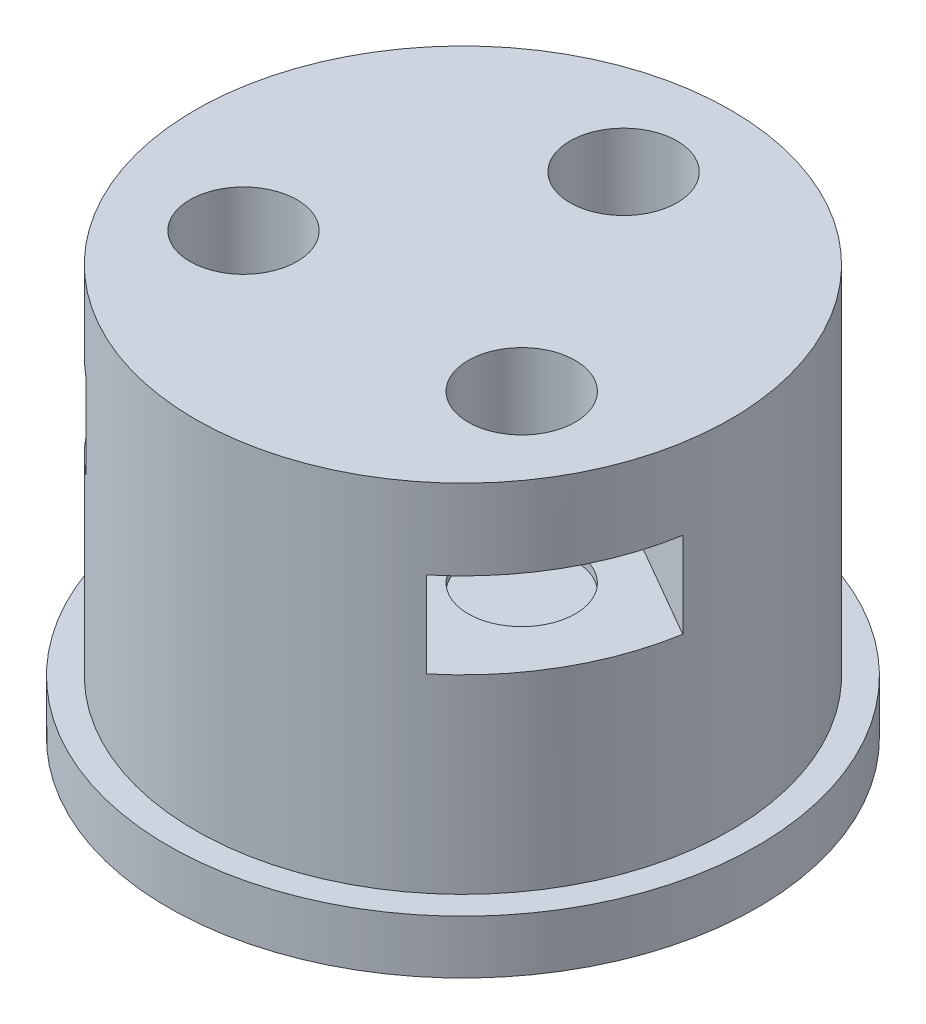
SolidWorks part; units mm, degrees
ref_plane "Front Plane" through (0, 0, 0) normal (0, 0, 1) x (1, 0, 0)
ref_plane "Top Plane" through (0, 0, 0) normal (0, 1, 0) x (1, 0, 0)
ref_plane "Right Plane" through (0, 0, 0) normal (1, 0, 0) x (0, 0, -1)
sketch "Sketch1" plane through (0, 0, 0) normal (0, 1, 0) x (1, 0, 0)
  circle A0 centre (0, 0) radius 10
  circle A1 centre (0, 0) radius 6 construction
  dimension "D1" = 20
  dimension "D2" = 12
extrude "Boss-Extrude1" add sketch "Sketch1" along normal blind 15.3
sketch "Sketch2" plane through (0, 0, 0) normal (0, -1, 0) x (1, 0, 0)
  circle A0 centre (0, 0) radius 10 construction
  circle A1 centre (0, 0) radius 10
  circle A2 centre (0, 0) radius 11
extrude "Boss-Extrude2" add sketch "Sketch2" against normal blind 2
sketch "Sketch3" plane through (0, 0, 0) normal (0, -1, 0) x (1, 0, 0)
  circle A0 centre (0, 0) radius 6
  dimension "D1" = 12
extrude "Cut-Extrude1" cut sketch "Sketch3" against normal blind 5
sketch "Sketch4" plane through (0, 15.3, 0) normal (0, 1, 0) x (1, 0, 0)
  circle A0 centre (0, 0) radius 6 construction
  circle A1 centre (0, 6) radius 2
  circle A2 centre (5.1962, -3) radius 2
  circle A3 centre (-5.1962, -3) radius 2
  point P14 (0, 0)
  dimension "D1" = 12
  dimension "D2" = 4
  dimension "D3" = 3
extrude "Cut-Extrude2" cut sketch "Sketch4" against normal blind 6.5
sketch "Sketch5" plane through (0, 15.3, 0) normal (0, 1, 0) x (1, 0, 0)
  line L0 (-3.5, 8.0207) -> (-3.5, 9.3675)
  line L1 (0, 1.9585) -> (3.5, 3.9793)
  line L2 (3.5, 3.9793) -> (3.5, 8.0207)
  line L3 (3.5, 8.0207) -> (0, 10.0415)
  line L4 (0, 10.0415) -> (-3.5, 8.0207)
  line L5 (-3.5, 8.0207) -> (-3.5, 3.9793)
  line L6 (-3.5, 3.9793) -> (0, 1.9585)
  line L7 (3.5, 8.0207) -> (3.5, 9.3675)
  line L8 (8.6962, -0.9793) -> (9.8625, -1.6527)
  line L9 (8.6962, -0.9793) -> (5.1962, 1.0415)
  line L10 (8.6962, -5.0207) -> (8.6962, -0.9793)
  line L11 (5.1962, -7.0415) -> (8.6962, -5.0207)
  line L12 (5.1962, -7.0415) -> (6.3625, -7.7148)
  line L13 (1.6962, -5.0207) -> (5.1962, -7.0415)
  line L14 (1.6962, -0.9793) -> (1.6962, -5.0207)
  line L15 (5.1962, 1.0415) -> (1.6962, -0.9793)
  line L16 (-5.1962, -7.0415) -> (-6.3625, -7.7148)
  line L17 (-5.1962, -7.0415) -> (-1.6962, -5.0207)
  line L18 (-8.6962, -5.0207) -> (-5.1962, -7.0415)
  line L19 (-8.6962, -0.9793) -> (-8.6962, -5.0207)
  line L20 (-8.6962, -0.9793) -> (-9.8625, -1.6527)
  line L21 (-5.1962, 1.0415) -> (-8.6962, -0.9793)
  line L22 (-1.6962, -0.9793) -> (-5.1962, 1.0415)
  line L23 (-1.6962, -5.0207) -> (-1.6962, -0.9793)
  circle A0 centre (0, 6) radius 3.5 construction
  circle A1 centre (0, 0) radius 6 construction
  circle A3 centre (-5.1962, -3) radius 2
  circle A4 centre (-5.1962, -3) radius 2
  circle A5 centre (5.1962, -3) radius 2
  circle A6 centre (5.1962, -3) radius 2
  circle A7 centre (0, 6) radius 2
  circle A8 centre (0, 6) radius 2
  circle A9 centre (0, 0) radius 10 construction
  circle A10 centre (0, 0) radius 10
  point P50 (0, 0)
  circle M11 centre (0, 6) radius 2
  circle M12 centre (5.1962, -3) radius 2
  circle M13 centre (-5.1962, -3) radius 2
  circle M15 centre (0, 0) radius 10
  dimension "D5" = 7
  dimension "D4" = 0
  dimension "D6" = 3
extrude "Cut-Extrude3" cut sketch "Sketch5" against normal blind 3.2 from offset 3 contours L18 L16 M15 | L17 L23 L22 L21 L19 L18 M15 M13 | L19 L20 M15 | L5 L6 L1 L2 L3 L4 M15 M11 | L4 L0 M15 | L3 L7 M15 | L10 L8 M15 | L9 L15 L14 L13 L11 L10 M15 M12 | L11 L12 M15 region at (-2.2825, 15.3, -9.2115) region at (-1.7328, 15.3, -8.9179) region at (-9.1186, 15.3, 2.629) region at (2.2825, 15.3, -9.2115) region at (-6.8927, 15.3, 0.0615) region at (-6.8361, 15.3, 6.5825) region at (9.1186, 15.3, 2.629) region at (6.8361, 15.3, 6.5825) region at (8.5892, 15.3, 2.9583) offset against normal yes
sketch "Sketch6" plane through (0, 0, 0) normal (0, -1, 0) x (1, 0, 0)
  circle A0 centre (0, 0) radius 6
  circle A1 centre (0, 0) radius 5
  circle A2 centre (0, 0) radius 6 construction
extrude "Boss-Extrude3" add sketch "Sketch6" against normal up to surface (5 mm away) from offset 3.5 up to face at (0, 5, -6) offset against normal yes
equation "\"Ns\"= 20"
equation "\"Np_b\"= 26"
equation "\"Np_s\"= 22"
equation "\"Nr_b\"= \"Ns\" + \"Np_b\" * 2"
equation "\"module\"= 1"
equation "\"pressure_angle\"= 20deg"
equation "\"h_a\"= 1 * \"module\"'addendum"
equation "\"h_f\"= 1.25 * \"module\"'dedendum"
equation "\"clr_tip_root\"= \"h_f\" - \"h_a\"'clearance of gear tooth tip and root"
equation "\"dp_r_b\"= \"module\" * \"Nr_b\"'PCD"
equation "\"db_r_b\"= \"dp_r_b\" * cos ( \"pressure_angle\" )'base CD"
equation "\"fw_r_b\"= \"fw_p_b\"'face width"
equation "\"alpha_r_b\"= sqr ( \"dp_r_b\" ^ 2 - \"db_r_b\" ^ 2 ) / \"db_r_b\" * 180 / pi - \"pressure_angle\""
equation "\"beta_r_b\"= ( 360 / ( 4 * \"Nr_b\" ) + \"alpha_r_b\" ) * 2"
equation "\"bearing_ID\"= \"module\" * ( \"Ns\" + \"Np_b\") + 6"
equation "\"bearing_OD\"= 1.18 * \"bearing_ID\" + 8.57"
equation "\"bearing_height\"= 0.09 * \"bearing_ID\" + 4.62"
equation "\"clearance_planet\"=1.5"
equation "\"case_dist\"= \"sec_carrier_thickness\" + \"clearance_planet\" + \"sun_coupler_hub_thickness\" - \"case_mounting_surface_height\""
equation "\"Motor_case_OD_max\"= \"case_mounting_PCD\" + \"case_mounting_hole_allen_socket_dia\" + \"clearance_case_mount_holes_shell_thickness\" * 2"
equation "\"case_mounting_PCD\"= \"motor_case_OD_base\" + \"case_mounting_hole_shift\" * 2"
equation "\"bearing mount thickness\"= IIF((\"bearing_OD\" + \"output_mounting_hole_dia\" * 4) > (\"Nr_s\" * \"module\" + 2 * \"h_b\"), \"output_mounting_hole_dia\" * 2, ((\"Nr_s\" * \"module\" + 2 * \"h_b\" - (\"bearing_OD\" + \"output_mounting_hole_dia\" * 4)) / 2) + \"output_mounting_hole_dia\" * 2 + \"standard_clearance_1_5mm\")"
equation "\"case_mounting_hole_dia\"=3"
equation "\"output_mounting_PCD\"= \"bearing_OD\" + \"bearing mount thickness\""
equation "\"output_mounting_hole_dia\"= 4"
equation "\"clearance_case_mount_holes_shell_thickness\"= 1"
equation "\"motor_case_OD_base\"= \"motor_OD\" + \"clearance_motor_and_case\" * 2 + \"Motor_case_thickness\" * 2"
equation "\"sec_carrier_thickness\"= 5"
equation "\"sun_coupler_hub_thickness\"= 4"
equation "\"clearance_sun_coupler_sec_carrier\"= 1.5"
equation "\"clearance_motor_and_case\"= IIF( ((\"Ns\" + \"Np_b\" * 2) * \"module\") < \"motor_OD\", 5, (((\"Ns\" + \"Np_b\" * 2) * \"module\" - \"motor_OD\") * 0.5 + 5) )"
equation "\"motor_OD\"= 72"
equation "\"Motor_case_thickness\"= 2.5"
equation "\"Motor_case_ID\"= \"motor_OD\" + \"clearance_motor_and_case\" * 2"
equation "\"case_mounting_hole_shift\"= \"case_mounting_hole_dia\" / 2 - 0.5"
equation "\"output_mounting_nut_wrench_size\"= 7"
equation "\"output_mounting_nut_thickness\"= 3.2"
equation "\"case_mounting_hole_allen_socket_dia\"= 5.5"
equation "\"output_mounting_nut_depth\"= 3"
equation "\"case_mounting_bolt_depth\"= 4.5"
equation "\"ring_radial_thickness\"= 5"
equation "\"ring_OD_b\"= \"Nr_b\" * \"module\" + \"ring_radial_thickness\" * 2"
equation "\"ring_to_chamfer_clearance\"= \"clearance_planet\""
equation "\"Motor_case_OD_base_to_chamfer\"=5"
equation "\"pattern_offset_from_motor_case_OD_base\"= 3"
equation "\"pattern_bulge_dia\"= 3"
equation "\"pattern_num_bulge\"= 18"
equation "\"pattern_depth\"= 2"
equation "\"motor_height\"= 27"
equation "\"case_mounting_wrench_size\"= 5.5"
equation "\"case_mounting_nut_clearance\"= 2"
equation "\"base_plate_thickness\"= 4"
equation "\"case_mounting_nut_thickness\"= 2.4"
equation "\"case_mounting_surface_height\"= 4"
equation "\"motor_mount_hole_PCD\"= 32"
equation "\"motor_mount_hole_dia\"= 4"
equation "\"motor_mount_hole_num\"= 4"
equation "\"central_hole_offset_from_motor_mount_PCD\"= 5"
equation "\"wire_slot_dist_from_center\"= 33"
equation "\"wire_slot_length\"= 10"
equation "\"wire_slot_radius\"= 4"
equation "\"driver_upper_holes_dist_from_center\"= 23"
equation "\"driver_lower_holes_dist_from_center\"= 15"
equation "\"driver_side_holes_dist_from_center\"= 20"
equation "\"driver_mount_holes_dia\"= 2.5"
equation "\"driver_mount_inserts_OD\"= 3.5"
equation "\"driver_mount_thickness\"= 1.5"
equation "\"driver_mount_height\"= 4"
equation "\"air_flow_hole_offset\"= 3"
equation "\"pressure angle\"= 20deg"
equation "\"h_b\"= 1.25 * \"module\"'dedendum"
equation "\"fw_p_s\"= \"fw_r_s\" + \"clearance_planet\""
equation "\"num_planet\"= 4"
equation "\"planet_pin_bolt_dia\"= 5"
equation "\"planet_pin_socket_head_dia\"= 8.5"
equation "\"carrier_PCD\"= ( \"Np_b\" + \"Ns\" ) * \"module\""
equation "\"planet_shaft_dia\"= 8"
equation "\"planet_shaft_step_offset\"= 1"
equation "\"carrier_trapezoidal_support_sun_offset\"= 5"
equation "\"carrier_trapezoidal_support_hole_PCD_offset_bearing_ID\"= 4"
equation "\"carrier_trapezoidal_support_hole_dia\"= 3"
equation "\"carrier_trapezoidal_support_hole_socket_head_dia\"= 5.5"
equation "\"carrier_bearing_step_width\"= 1.5"
equation "\"standard_clearance_1_5mm\"=1.5"
equation "\"standard_fillet_1_5mm\"= 1.5"
equation "\"sun_shaft_bearing_OD\"= 12"
equation "\"sun_shaft_bearing_width\"= 3.5"
equation "\"standard_bearing_insertion_chamfer\"= 0.5"
equation "\"carrier_trapezoidal_support_hole_wrench_size\"= 5.5"
equation "\"planet_pin_bolt_wrench_size\"= 8"
equation "\"planet_bearing_OD\"= 12"
equation "\"planet_bearing_width\"= 3.5"
equation "\"planet_bore\"= 10"
equation "\"motor_output_hole_PCD\"= 22"
equation "\"motor_output_hole_dia\"= 3"
equation "\"motor_output_hole_num\"= 4"
equation "\"dp_s\"= \"module\" * \"Ns\"'PCD"
equation "\"db_s\"= \"dp_s\" * cos ( \"pressure angle\" )'base CD"
equation "\"fw_s_calc\"= 10mm'face width"
equation "\"alpha_s\"= sqr ( \"dp_s\" ^ 2 - \"db_s\" ^ 2 ) / \"db_s\" * 180 / pi - \"pressure angle\""
equation "\"beta_s\"= ( 360 / ( 4 * \"Ns\" ) - \"alpha_s\" ) * 2"
equation "\"dp_p_b\"= \"module\" * \"Np_b\"'PCD"
equation "\"db_p_b\"= \"dp_p_b\" * cos ( \"pressure angle\" )'base CD"
equation "\"alpha_p_b\"= sqr ( \"dp_p_b\" ^ 2 - \"db_p_b\" ^ 2 ) / \"db_p_b\" * 180 / pi - \"pressure angle\""
equation "\"beta_p_b\"= ( 360 / ( 4 * \"Np_b\" ) - \"alpha_p_b\" ) * 2"
equation "\"sun_shaft_bearing_ID\"= 8"
equation "\"sun_hub_dia\"= \"motor_output_hole_PCD\" + \"motor_output_hole_dia\" + \"standard_clearance_1_5mm\" * 2"
equation "\"sun_central_bolt_dia\"= 5"
equation "\"sun_central_bolt_socket_head_dia\"= 8.5"
equation "\"fw_s_used\"= \"fw_p_s\" + \"fw_p_b\" + \"clearance_planet\" + \"sec_carrier_thickness\" + \"standard_clearance_1_5mm\" - \"carrier_small_ring_inner_bearing_flap\" +  \"standard_clearance_1_5mm\" "
equation "\"motor_output_hole_CSK_OD\"= 9'8.96 is exact value"
equation "\"motor_output_hole_CSK_head_height\"= 2.5"
equation "\"bearing_retainer_thickness\"= 2"
equation "\"fw_p_b\"= 8"
equation "\"dp_p_s\"= \"module\" * \"Np_s\"'PCD"
equation "\"db_p_s\"= \"dp_p_s\" * cos ( \"pressure angle\" )'base CD"
equation "\"alpha_p_s\"= sqr ( \"dp_p_s\" ^ 2 - \"db_p_s\" ^ 2 ) / \"db_p_s\" * 180 / pi - \"pressure angle\""
equation "\"beta_p_s\"= ( 360 / ( 4 * \"Np_s\" ) - \"alpha_p_s\" ) * 2"
equation "\"Nr_s\"= \"Ns\" + \"Np_b\" + \"Np_s\"'num teeth"
equation "\"clr_tip_root_s\"= \"h_f\" - \"h_a\"'clearance of gear tooth tip and root"
equation "\"dp_r_s\"= \"module\" * \"Nr_s\"'PCD"
equation "\"db_r_s\"= \"dp_r_s\" * cos ( \"pressure_angle\" )'base CD"
equation "\"fw_r_s\"= 8mm'face width"
equation "\"alpha_r_s\"= sqr ( \"dp_r_s\" ^ 2 - \"db_r_s\" ^ 2 ) / \"db_r_s\" * 180 / pi - \"pressure_angle\""
equation "\"beta_r_s\"= ( 360 / ( 4 * \"Nr_s\" ) + \"alpha_r_s\" ) * 2"
equation "\"D1@Boss-Extrude1\"=\"bearing_height\" + \"carrier_thickness\" + \"carrier_small_ring_inner_bearing_flap\""
equation "\"D1@Cut-Extrude1\"=\"sun_shaft_bearing_width\" + \"standard_clearance_1_5mm\""
equation "\"D5@Sketch5\"=\"small_ring_output_wall_to_bearing_shaft_attachement_nut_wrench\""
equation "\"small_ring_case_thickness\"= 4mm"
equation "\"carrier_thickness\"= 4mm"
equation "\"small_ring_output_wall_thickness\"= 5mm"
equation "\"small_ring_output_wall_to_bearing_shaft_attachement_hole_dia\"= 4mm"
equation "\"small_ring_output_wall_to_bearing_shaft_attachement_hole_pcd\"= 12mm"
equation "\"small_ring_output_wall_to_bearing_shaft_attachement_hole_num\"= 3"
equation "\"small_ring_output_wall_to_bearing_shaft_attachement_hole_CSK_OD\"= 9mm"
equation "\"small_ring_output_wall_to_bearing_shaft_attachement_hole_CSK_head_height\"= 2.5mm"
equation "\"carrier_small_ring_inner_bearing_ID\"= 20mm"
equation "\"carrier_small_ring_inner_bearing_OD\"= 32mm"
equation "\"carrier_small_ring_inner_bearing_height\"= 7mm"
equation "\"D1@Sketch1\"=\"carrier_small_ring_inner_bearing_ID\""
equation "\"D2@Sketch1\"=\"sun_shaft_bearing_OD\""
equation "\"D1@Sketch2\"=\"standard_clearance_1_5mm\"*2/3"
equation "\"D1@Sketch3\"=\"sun_shaft_bearing_OD\""
equation "\"D1@Sketch4\"=\"small_ring_output_wall_to_bearing_shaft_attachement_hole_pcd\""
equation "\"D2@Sketch4\"=\"small_ring_output_wall_to_bearing_shaft_attachement_hole_dia\""
equation "\"D3@Sketch4\"=\"small_ring_output_wall_to_bearing_shaft_attachement_hole_num\""
equation "\"D6@Sketch5\"=\"small_ring_output_wall_to_bearing_shaft_attachement_hole_num\""
equation "\"D19@Cut-Extrude3\"=\"standard_clearance_1_5mm\"*2"
equation "\"D1@Sketch6\"=\"standard_clearance_1_5mm\"*2/3"
equation "\"D19@Boss-Extrude3\"=\"sun_shaft_bearing_width\""
equation "\"small_ring_output_wall_to_bearing_shaft_attachement_hole_depth\"= 6.5mm"
equation "\"small_ring_output_wall_to_bearing_shaft_attachement_nut_wrench\"= 7mm"
equation "\"small_ring_output_wall_to_bearing_shaft_attachement_nut_thickness\"= 3.2mm"
equation "\"carrier_small_ring_inner_bearing_flap\"= 2mm"
equation "\"D1@Boss-Extrude2\"=\"carrier_small_ring_inner_bearing_flap\""
equation "\"D1@Cut-Extrude2\"=\"small_ring_output_wall_to_bearing_shaft_attachement_hole_depth\""
equation "\"D1@Cut-Extrude3\"=\"small_ring_output_wall_to_bearing_shaft_attachement_nut_thickness\""
